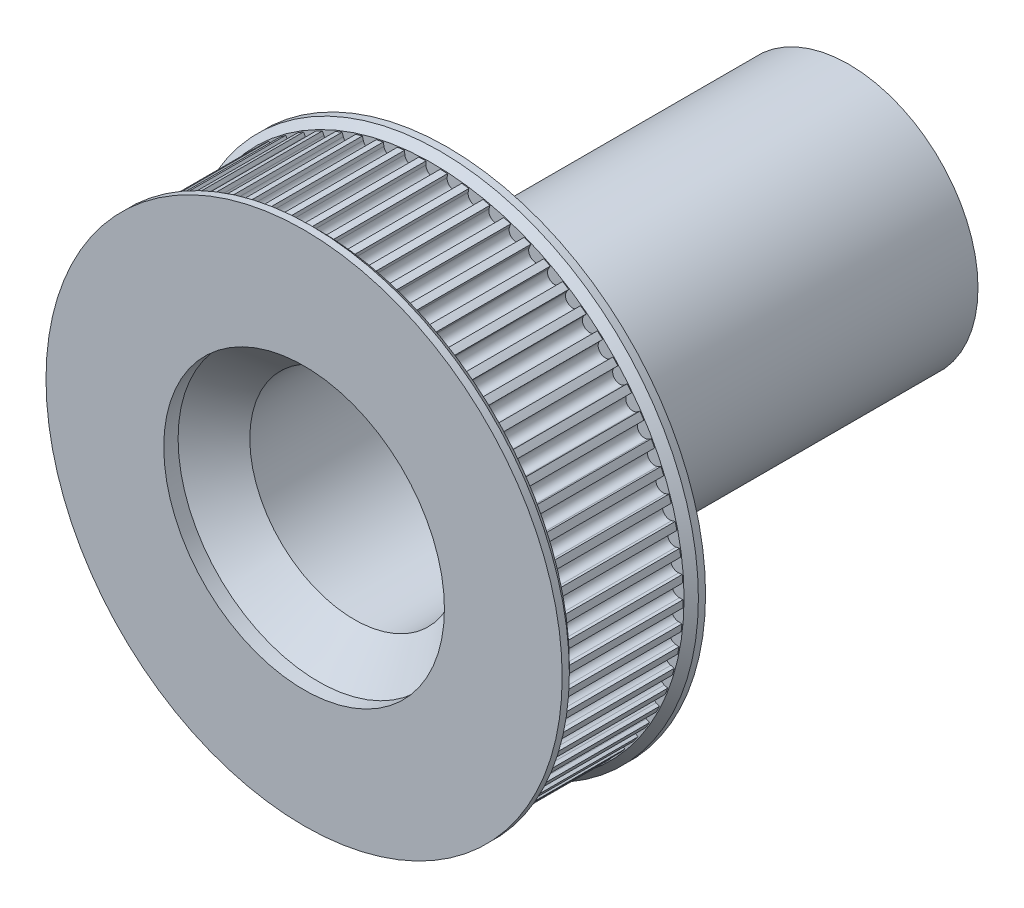
SolidWorks part; units mm, degrees
material "PA Type 6"
ref_plane "Front Plane" through (0, 0, 0) normal (0, 0, 1) x (1, 0, 0)
ref_plane "Top Plane" through (0, 0, 0) normal (0, 1, 0) x (1, 0, 0)
ref_plane "Right Plane" through (0, 0, 0) normal (1, 0, 0) x (0, 0, -1)
sketch "Sketch1" plane through (0, 0, 0) normal (0, 0, 1) x (1, 0, 0)
  circle A0 centre (0, 0) radius 18
extrude "Boss-Extrude1" add sketch "Sketch1" along normal blind 74
sketch "Sketch2" plane through (0, 0, 74) normal (0, 0, 1) x (1, 0, 0)
  circle A0 centre (0, 0) radius 14.576
extrude "Cut-Extrude1" cut sketch "Sketch2" against normal blind 85
sketch "Sketch3" plane through (0, 0, 0) normal (0, 0, -1) x (-1, 0, 0)
  circle A0 centre (0, 0) radius 4.5
  circle A1 centre (0, 0) radius 18 construction
  dimension "D1" = 9
extrude "Cut-Extrude2" cut sketch "Sketch3" against normal blind 60 rebuild error yes
sketch "Sketch4" plane through (0, 0, 74) normal (0, 0, 1) x (1, 0, 0)
  circle A0 centre (0, 0) radius 14.576
  circle A1 centre (0, 0) radius 34.85
  dimension "D1" = 69.7
extrude "Boss-Extrude2" add sketch "Sketch4" against normal blind 18
sketch "Sketch5" plane through (0, 0, 74) normal (0, 0, 1) x (1, 0, 0)
  circle A0 centre (1.619, -28.1194) radius 3.1814
extrude "Cut-Extrude3" cut sketch "Sketch5" against normal blind 4 from offset 13 offset against normal yes
chamfer "Chamfer2" distance 5 angle 45 rebuild error yes
chamfer "Chamfer3" distance 5 angle 45 1 edges at (14.576, 0, 74)
sketch "Sketch6" plane through (0, 0, 74) normal (0, 0, 1) x (1, 0, 0)
  line L0 (0, 35.6693) -> (0, 34.3375) construction
  line L1 (1, 35.6693) -> (1, 34.3375)
  line L2 (-1, 35.6693) -> (-1, 34.3375)
  arc A0 (1, 35.6693) -> (-1, 35.6693) centre (0, 35.6693) ccw
  arc A1 (-1, 34.3375) -> (1, 34.3375) centre (0, 34.3375) ccw
  point P2 (0, 35.0034)
  dimension "D1" = 1
extrude "Cut-Extrude4" cut sketch "Sketch6" against normal blind 18
pattern_circular "CirPattern1" count 73 over 360 about axis through (0, 0, 74) along (0, 0, 1) of "Cut-Extrude4"
sketch "Sketch7" plane through (0, 0, 74) normal (0, 0, 1) x (1, 0, 0)
  circle A0 centre (0, 0) radius 19.576
  circle A1 centre (0, 0) radius 36
extrude "Boss-Extrude3" add sketch "Sketch7" along normal blind 2
pattern_linear "LPattern1" count 2 spacing 18 along (0, 0, -1) of "Boss-Extrude3"
chamfer "Chamfer4" distance 1 angle 45 2 edges at (36, 0, 74) (36, 0, 58)
sketch "Эскиз1" plane through (0, 0, 56) normal (0, 0, -1) x (-1, 0, 0)
  circle A0 centre (-9.4119, 27.7754) radius 3.5
extrude "Вырез-Вытянуть1" cut sketch "Эскиз1" against normal blind 4
sketch "Эскиз2" plane through (0, 0, 0) normal (0, 0, -1) x (-1, 0, 0)
  line L1 (-2, 8.5265) -> (2, 8.5265)
  line L2 (-2, 8.5265) -> (-2, 0.0452)
  line L3 (-2, 0.0452) -> (2, 0.0452)
  line L4 (2, 8.5265) -> (2, 0.0452)
  line L5 (-2, 8.5265) -> (2, 0.0452) construction
  line L6 (-2, 0.0452) -> (2, 8.5265) construction
  point P0 (0, 4.2859)
  dimension "D1" = 4
extrude "Вырез-Вытянуть2" cut sketch "Эскиз2" against normal blind 12 rebuild error yes
